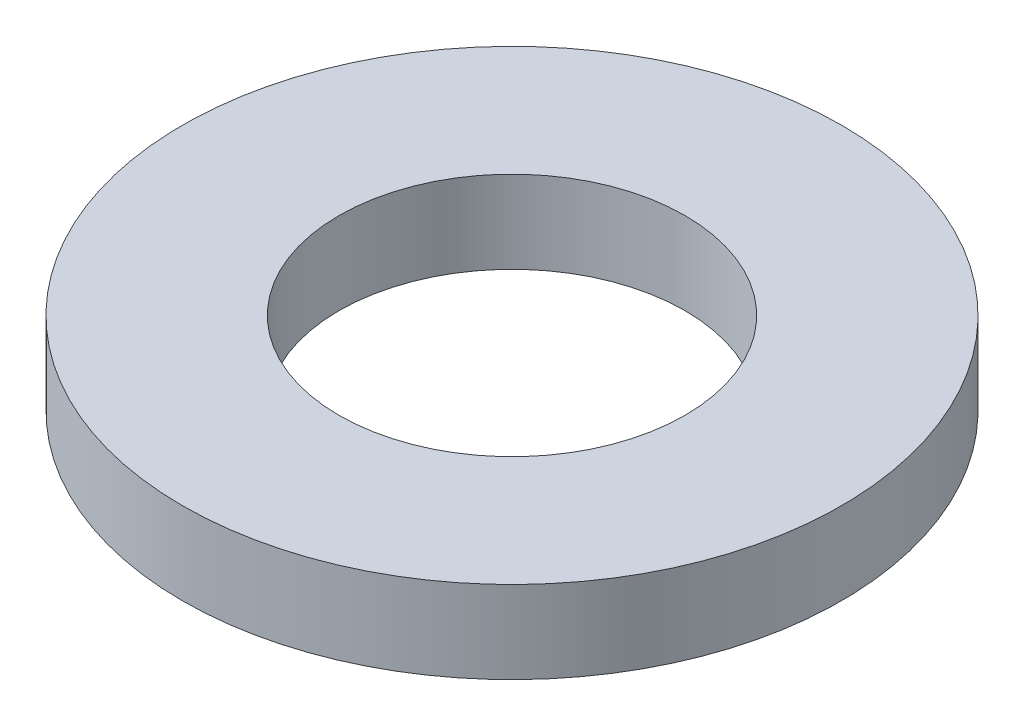
SolidWorks part; units mm, degrees
ref_plane "Front Plane" through (0, 0, 0) normal (0, 0, 1) x (1, 0, 0)
ref_plane "Top Plane" through (0, 0, 0) normal (0, 1, 0) x (1, 0, 0)
ref_plane "Right Plane" through (0, 0, 0) normal (1, 0, 0) x (0, 0, -1)
sketch "Sketch1" plane through (0, 0, 0) normal (0, 1, 0) x (1, 0, 0)
  circle A0 centre (0, 0) radius 10.16
  circle A1 centre (0, 0) radius 5.334
  dimension "D1" = 20.32
  dimension "D2" = 10.668
extrude "Boss-Extrude1" add sketch "Sketch1" along normal blind 2.54
